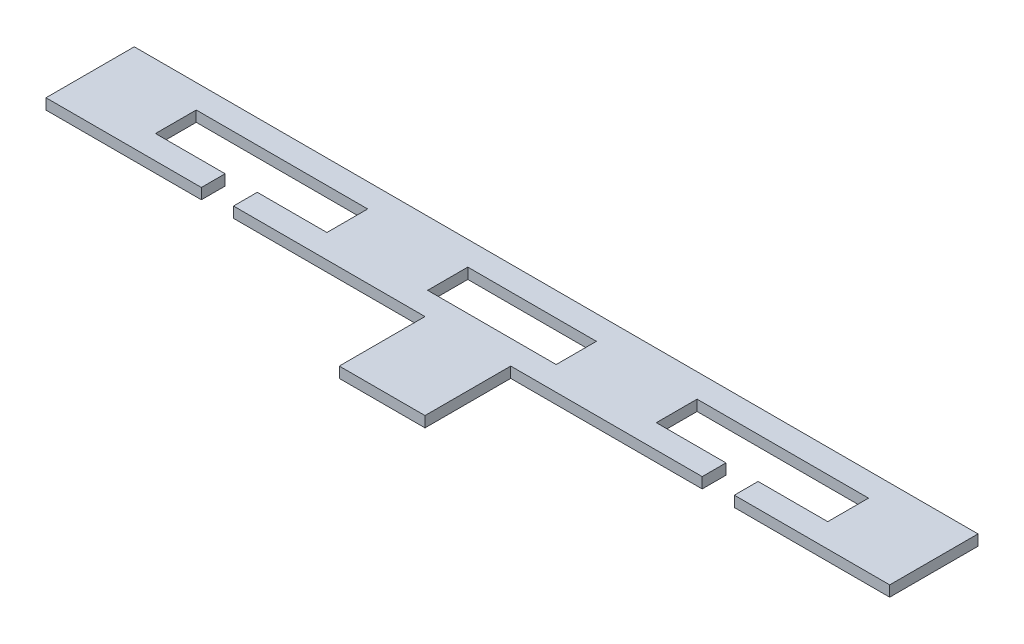
SolidWorks part; units mm, degrees
ref_plane "Front Plane" through (0, 0, 0) normal (0, 0, 1) x (1, 0, 0)
ref_plane "Top Plane" through (0, 0, 0) normal (0, 1, 0) x (1, 0, 0)
ref_plane "Right Plane" through (0, 0, 0) normal (1, 0, 0) x (0, 0, -1)
sketch "Sketch1" plane through (0, 0, 0) normal (0, 1, 0) x (1, 0, 0)
  line L0 (0, 52.3215) -> (1000.0005, 52.3215) construction
  line L2 (0, 0) -> (0, 104.643)
  line L3 (0, 104.643) -> (1000.0005, 104.643)
  line L4 (1000.0005, 0) -> (1000.0005, 104.643)
  line L9 (101.6, 28.162) -> (184.15, 28.162)
  line L10 (101.6, 28.162) -> (101.6, 76.4809)
  line L12 (304.8, 28.162) -> (304.8, 76.4809)
  line L17 (0, -31.5189) -> (406.4, -31.5189) construction
  line L18 (0, -31.5189) -> (0, -107.7189) construction
  line L19 (0, -107.7189) -> (406.4, -107.7189) construction
  line L20 (406.4, -31.5189) -> (406.4, -107.7189) construction
  line L21 (593.6005, -31.5189) -> (1000.0005, -31.5189) construction
  line L22 (593.6005, -31.5189) -> (593.6005, -107.7189) construction
  line L23 (593.6005, -107.7189) -> (1000.0005, -107.7189) construction
  line L24 (1000.0005, -31.5189) -> (1000.0005, -107.7189) construction
  line L25 (203.2, -31.5189) -> (203.2, -107.7189) construction
  line L26 (796.8005, -107.7189) -> (796.8005, -31.5189) construction
  line L27 (203.2, -31.5189) -> (203.2, 104.643) construction
  line L28 (796.8005, -31.5189) -> (796.8005, 104.643) construction
  line L29 (500.0003, -101.6) -> (500.0003, 104.643) construction
  line L30 (0, 0) -> (184.15, 0)
  line L32 (449.2003, -101.6) -> (449.2003, 0)
  line L33 (550.8003, -101.6) -> (550.8003, 0)
  line L35 (101.6, 76.4809) -> (304.8, 76.4809)
  line L36 (423.8003, 76.1428) -> (576.2003, 76.1428)
  line L37 (423.8003, 76.1428) -> (423.8003, 28.5002)
  line L38 (423.8003, 28.5002) -> (576.2003, 28.5002)
  line L39 (576.2003, 76.1428) -> (576.2003, 28.5002)
  line L40 (423.8003, 76.1428) -> (576.2003, 28.5002) construction
  line L41 (423.8003, 28.5002) -> (576.2003, 76.1428) construction
  line L42 (695.2005, 28.162) -> (695.2005, 76.4809)
  line L43 (898.4005, 28.162) -> (815.8505, 28.162)
  line L44 (898.4005, 28.162) -> (898.4005, 76.4809)
  line L45 (898.4005, 76.4809) -> (695.2005, 76.4809)
  line L46 (550.8003, 0) -> (777.7505, 0)
  line L47 (550.8003, -101.6) -> (449.2003, -101.6)
  line L48 (203.2, 12.7813) -> (184.15, 12.7813) construction
  line L49 (203.2, 12.7813) -> (222.25, 12.7813) construction
  line L50 (184.15, 28.162) -> (184.15, 0)
  line L51 (222.25, 28.162) -> (222.25, 0)
  line L52 (222.25, 28.162) -> (304.8, 28.162)
  line L53 (222.25, 0) -> (449.2003, 0)
  line L54 (796.8005, 12.7813) -> (777.7505, 12.7813) construction
  line L55 (796.8005, 12.7813) -> (815.8505, 12.7813) construction
  line L56 (777.7505, 28.162) -> (777.7505, 0)
  line L57 (815.8505, 28.162) -> (815.8505, 0)
  line L58 (815.8505, 0) -> (1000.0005, 0)
  line L59 (777.7505, 28.162) -> (695.2005, 28.162)
  point P36 (500.0003, 52.3215)
  point P41 (101.6, 52.3215)
  dimension "D1" = 406.4
  dimension "D2" = 76.2
  dimension "D3" = 1000.0005
  dimension "D4" = 101.6
  dimension "D5" = 101.6
  dimension "D6" = 203.2
  dimension "D7" = 38.1
  dimension "D8" = 19.05
  dimension "D9" = 19.05
  dimension "D10" = 152.4
extrude "Boss-Extrude1" add sketch "Sketch1" along normal blind 12.7
